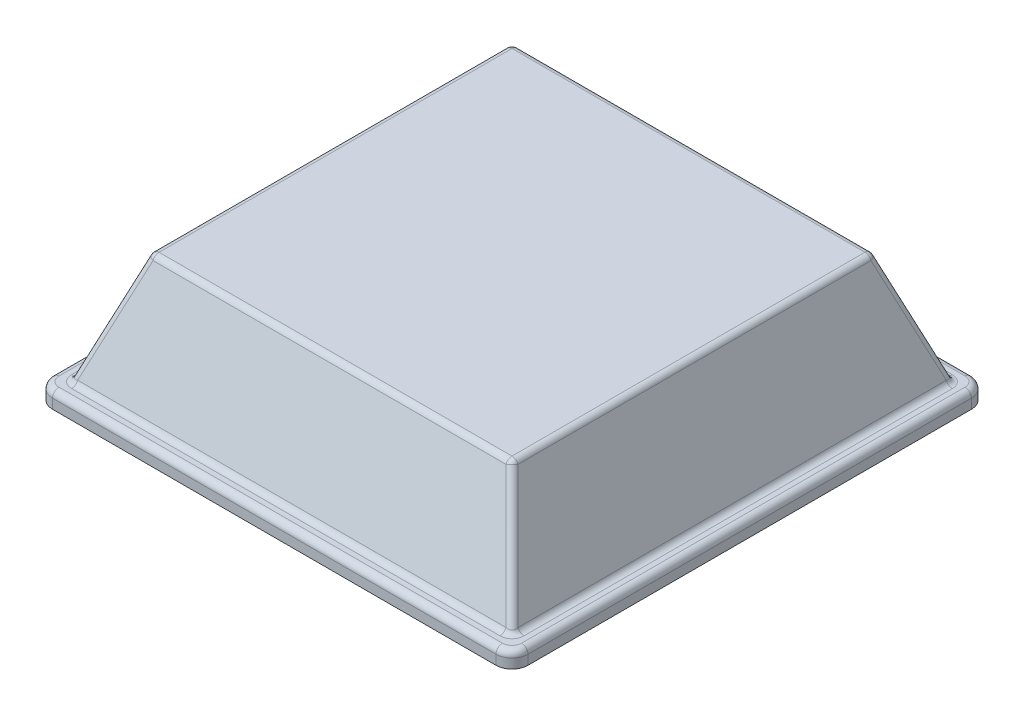
SolidWorks part; units mm, degrees
ref_plane "Front" through (0, 0, 0) normal (0, 0, 1) x (1, 0, 0)
ref_plane "Top" through (0, 0, 0) normal (0, 1, 0) x (1, 0, 0)
ref_plane "Right" through (0, 0, 0) normal (1, 0, 0) x (0, 0, -1)
sketch "Sketch1" plane through (0, 0, 0) normal (0, 1, 0) x (1, 0, 0)
  line L1 (-5.1594, 5.1594) -> (5.1594, 5.1594) construction
  line L2 (-5.1594, 5.1594) -> (-5.1594, -5.1594) construction
  line L3 (-5.1594, -5.1594) -> (5.1594, -5.1594) construction
  line L4 (5.1594, 5.1594) -> (5.1594, -5.1594) construction
  line L5 (-5.1594, 5.1594) -> (5.1594, -5.1594) construction
  line L6 (-5.1594, -5.1594) -> (5.1594, 5.1594) construction
  point P0 (0, 0)
  dimension "width" = 10.3187
  dimension "Length" = 10.3187
sketch "Sketch3" plane through (0, 0, 0) normal (1, 0, 0) x (0, 0, -1)
  line L0 (0, 0) -> (0, 2.7781) construction
  line L1 (5.1594, 0) -> (-5.1594, 0) construction
  dimension "Height" = 2.7781
sketch "Sketch2" plane through (0, 0, 0) normal (0, 1, 0) x (1, 0, 0)
  line L0 (-5.1594, 5.1594) -> (-5.1594, -5.1594) construction
  line L1 (-5.1594, 5.1594) -> (5.1594, 5.1594) construction
  line L2 (5.1594, 5.1594) -> (5.1594, -5.1594) construction
  line L3 (-5.1594, -5.1594) -> (5.1594, -5.1594) construction
  line L4 (-5.1594, 5.1594) -> (-5.1594, -5.1594)
  line L5 (-5.1594, 5.1594) -> (5.1594, 5.1594)
  line L6 (5.1594, 5.1594) -> (5.1594, -5.1594)
  line L7 (-5.1594, -5.1594) -> (5.1594, -5.1594)
extrude "Boss-Extrude1" add sketch "Sketch2" along normal blind 0.3473
sketch "Sketch4" plane through (0, 0.3473, 0) normal (0, 1, 0) x (1, 0, 0)
  line L8 (-4.8121, 4.8121) -> (-4.8121, -4.8121)
  line L9 (-4.8121, -4.8121) -> (4.8121, -4.8121)
  line L10 (4.8121, -4.8121) -> (4.8121, 4.8121)
  line L11 (4.8121, 4.8121) -> (-4.8121, 4.8121)
  line L12 (-4.8121, 4.8121) -> (-4.8121, -4.8121)
  line L13 (-4.8121, -4.8121) -> (4.8121, -4.8121)
  line L14 (4.8121, -4.8121) -> (4.8121, 4.8121)
  line L15 (4.8121, 4.8121) -> (-4.8121, 4.8121)
  dimension "D1" = 0.3473
extrude "Boss-Extrude2" add sketch "Sketch4" along normal up to vertex (2.4309 mm away) draft 20 up to point (0, 2.7781, 0)
fillet "Fillet1" radius 0.3473 4 edges at (-5.1594, 0.1736, 5.1594) (-5.1594, 0.1736, -5.1594) (5.1594, 0.1736, -5.1594) (5.1594, 0.1736, 5.1594)
fillet "Fillet2" radius 0.1389 20 edges at (5.0577, 0.3473, 5.0577) (0, 0.3473, 5.1594) (-5.0577, 0.3473, 5.0577) (-5.1594, 0.3473, 0) (-5.0577, 0.3473, -5.0577) (0, 0.3473, -5.1594) (5.0577, 0.3473, -5.0577) (0, 0.3473, -4.8121) (4.3697, 1.5627, -4.3697) (4.8121, 0.3473, 0) (4.3697, 1.5627, 4.3697) (0, 0.3473, 4.8121) (-4.3697, 1.5627, -4.3697) (-4.3697, 1.5627, 4.3697) (-4.8121, 0.3473, 0) (3.9273, 2.7781, 0) (0, 2.7781, 3.9273) (-3.9273, 2.7781, 0) (0, 2.7781, -3.9273) (5.1594, 0.3473, 0)
equation "\"D1@Boss-Extrude1\"=\"Height@Sketch3\"/8"
equation "\"D1@Sketch4\"=\"D1@Boss-Extrude1\""
equation "\"D1@Fillet1\"=\"D1@Boss-Extrude1\""
equation "\"D1@Fillet2\"=\"D1@Fillet1\"/2.5"
